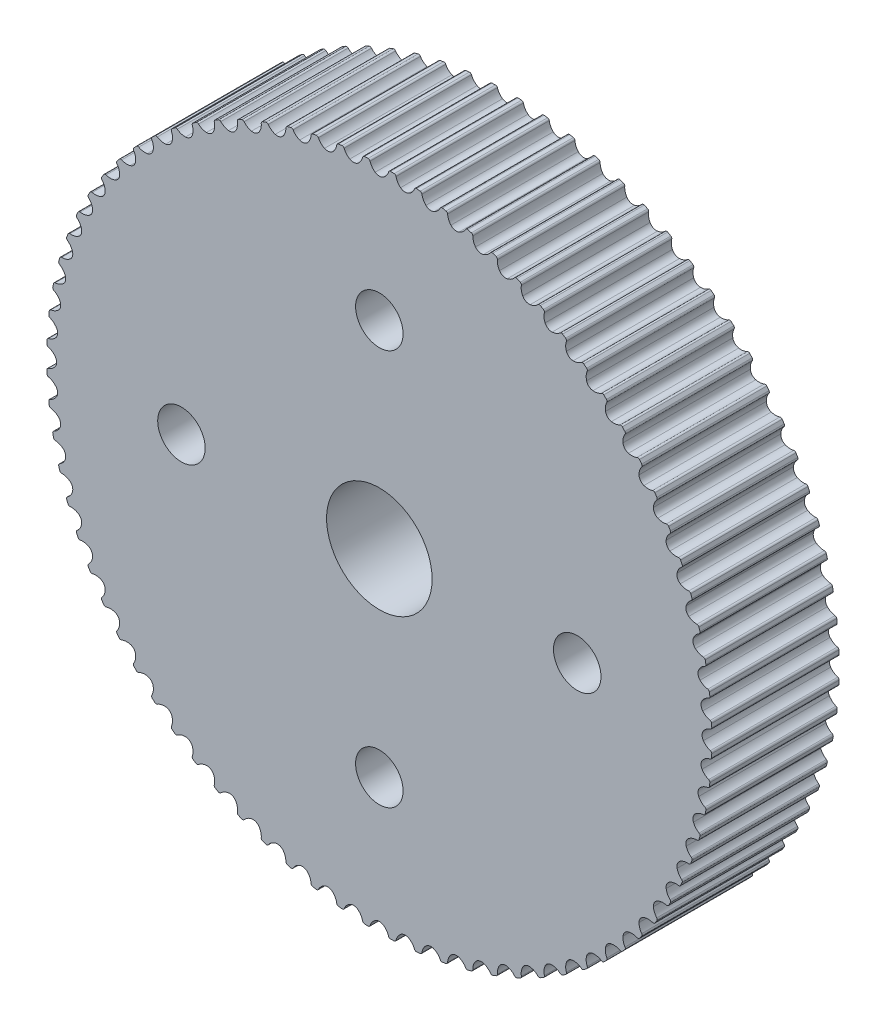
SolidWorks part; units mm, degrees
ref_plane "Front Plane" through (0, 0, 0) normal (0, 0, 1) x (1, 0, 0)
ref_plane "Top Plane" through (0, 0, 0) normal (0, 1, 0) x (1, 0, 0)
ref_plane "Right Plane" through (0, 0, 0) normal (1, 0, 0) x (0, 0, -1)
sketch "Sketch1" plane through (0, 0, 0) normal (0, 0, 1) x (1, 0, 0)
  line L3 (0, 25.2095) -> (1.9984, 25.1302) construction
  line L4 (0, 0) -> (0, 24.4595) construction
  line L5 (0, 24.4595) -> (0, 25.741) construction
  line L15 (1.9984, 25.1302) -> (2.047, 25.741)
  line L16 (2.047, 25.741) -> (-2.047, 25.741)
  line L17 (0, 24.4595) -> (0.1538, 24.4595) construction
  line L18 (-1.9984, 25.1302) -> (-2.047, 25.741)
  circle A0 centre (0, 0) radius 25.4635 construction
  circle A1 centre (0, 0) radius 25.2095 construction
  circle A2 centre (0, 0) radius 24.9555 construction
  arc A10 (0.8513, 25.1951) -> (1.9984, 25.1302) centre (0, 0) cw
  arc A11 (-0.3168, 24.5588) -> (0.3168, 24.5588) centre (0, 25.0145) ccw
  arc A12 (0.3168, 24.5588) -> (0.7027, 25.0889) centre (-0.254, 25.3799) ccw
  arc A13 (0.7027, 25.0889) -> (0.8513, 25.1951) centre (0.8462, 25.0452) cw
  arc A14 (-0.8513, 25.1951) -> (-1.9984, 25.1302) centre (0, 0) ccw
  arc A15 (-0.7027, 25.0889) -> (-0.8513, 25.1951) centre (-0.8462, 25.0452) ccw
  arc A16 (-0.3168, 24.5588) -> (-0.7027, 25.0889) centre (0.254, 25.3799) cw
  point P11 (0, 25.4635)
  point P13 (0, 25.2095)
  point P14 (0, 24.9555)
  dimension "D2" = 0.2775
sketch "Sketch2" plane through (0, 0, 0) normal (1, 0, 0) x (0, 0, -1)
  line L0 (-9.525, 4) -> (9.525, 4)
  line L1 (-9.525, 4) -> (-9.525, 19.05)
  line L2 (-9.525, 19.05) -> (-0.125, 19.05)
  line L3 (-0.125, 19.05) -> (-0.125, 25.2095)
  line L9 (9.525, 25.2095) -> (9.525, 4)
  line L10 (-9.525, 0) -> (9.525, 0) construction
  line L16 (-0.125, 25.2095) -> (9.525, 25.2095)
  point P25 (9.525, 0)
  point P26 (-0.125, 0)
  dimension "OA" = 19.05
  dimension "Bore" = 8
  dimension "Hub Dia" = 38.1
  dimension "Outside Width" = 9.65
revolve "Revolve1" add sketch "Sketch2" angle 360 mid plane about L10
sketch "Sketch3" plane through (0, 0, 0) normal (0, 0, 1) x (1, 0, 0)
  line L3 (1.9984, 25.1302) -> (2.047, 25.741) construction
  line L4 (-1.9984, 25.1302) -> (-2.047, 25.741) construction
  line L5 (2.047, 25.741) -> (-2.047, 25.741) construction
  line L6 (1.9984, 25.1302) -> (2.047, 25.741)
  line L7 (-1.9984, 25.1302) -> (-2.047, 25.741)
  line L8 (2.047, 25.741) -> (-2.047, 25.741)
  arc A0 (1.9984, 25.1302) -> (0.8513, 25.1951) centre (0, 0) ccw construction
  arc A1 (0.8513, 25.1951) -> (0.7027, 25.0889) centre (0.8462, 25.0452) ccw construction
  arc A3 (0.3168, 24.5588) -> (0.7027, 25.0889) centre (-0.254, 25.3799) ccw construction
  arc A4 (-0.3168, 24.5588) -> (0.3168, 24.5588) centre (0, 25.0145) ccw construction
  arc A5 (-0.7027, 25.0889) -> (-0.3168, 24.5588) centre (0.254, 25.3799) ccw construction
  arc A6 (-0.7027, 25.0889) -> (-0.8513, 25.1951) centre (-0.8462, 25.0452) ccw construction
  arc A7 (-0.8513, 25.1951) -> (-1.9984, 25.1302) centre (0, 0) ccw construction
  arc A8 (1.9984, 25.1302) -> (0.8513, 25.1951) centre (0, 0) ccw
  arc A9 (0.8513, 25.1951) -> (0.7027, 25.0889) centre (0.8462, 25.0452) ccw
  arc A10 (0.3168, 24.5588) -> (0.7027, 25.0889) centre (-0.254, 25.3799) ccw
  arc A11 (-0.3168, 24.5588) -> (0.3168, 24.5588) centre (0, 25.0145) ccw
  arc A12 (-0.7027, 25.0889) -> (-0.3168, 24.5588) centre (0.254, 25.3799) ccw
  arc A13 (-0.7027, 25.0889) -> (-0.8513, 25.1951) centre (-0.8462, 25.0452) ccw
  arc A14 (-0.8513, 25.1951) -> (-1.9984, 25.1302) centre (0, 0) ccw
extrude "Cut-Extrude1" cut sketch "Sketch3" against normal through all from surface starting at face at (19.05, 0, 0.125)
pattern_circular "CirPattern1" count 80 over 360 about axis through (0, 0, 9.525) along (0, 0, 1) of "Cut-Extrude1"
sketch "Sketch4" plane through (0, 0, 0) normal (1, 0, 0) x (0, 0, -1)
  line L0 (-9.525, 0) -> (-0.125, 0) construction
  line L1 (-9.525, 19.05) -> (-9.525, -19.05) construction
  line L2 (-0.125, 19.05) -> (-0.125, -19.05) construction
  circle A0 centre (-4.825, 0) radius 2.0828
  dimension "D1" = 4.1656
extrude "Cut-Extrude2" cut sketch "Sketch4" along normal through all
ref_plane "Plane1" through (0, 0, 4.825) normal (0, 0, 1) x (1, 0, 0)
sketch "Sketch5" plane through (0, 0, 4.825) normal (0, 0, 1) x (1, 0, 0)
  line L0 (3.415, -2.0828) -> (18.9358, -2.0828) construction
  line L1 (4.381, -2.0828) -> (18.5548, -2.0828)
  line L2 (18.9358, -1.7018) -> (18.9358, 0)
  line L3 (18.9358, 0) -> (4, 0) construction
  line L4 (4, -1.7018) -> (4, 0)
  line L5 (4.381, -2.0828) -> (4, -1.7018)
  line L6 (18.5548, -2.0828) -> (18.9358, -1.7018)
  line L13 (3.415, -2.0828) -> (18.9358, -2.0828) construction
  line L23 (4, 0) -> (18.9358, 0)
  circle A0 centre (0, 0) radius 19.05 construction
  circle A1 centre (0, 0) radius 4 construction
  point P0 (4, -2.0828)
  point P3 (18.9358, -2.0828)
  point P4 (-19.05, 0)
  point P6 (-4, 0)
ref_axis "Center Axis 1" through (0, 0, -9.525) along (0, 0, 1)
ref_plane "Contact Plane 1" through (0, 0, 9.525) normal (0, 0, 1) x (1, 0, 0)
ref_plane "Contact Plane 2" through (0, 0, -9.525) normal (0, 0, -1) x (-1, 0, 0)
sketch "Sketch6" plane through (0, 0, 0.125) normal (0, 0, 1) x (1, 0, 0)
  line L1 (25.4, -25.4) -> (-25.4, -25.4)
  line L2 (25.4, -25.4) -> (25.4, 25.4)
  line L3 (25.4, 25.4) -> (-25.4, 25.4)
  line L4 (-25.4, -25.4) -> (-25.4, 25.4)
  line L5 (25.4, -25.4) -> (-25.4, 25.4) construction
  line L6 (25.4, 25.4) -> (-25.4, -25.4) construction
  circle A0 centre (0, 0) radius 4 construction
  circle A1 centre (0, 0) radius 4
  point P0 (0, 0)
  dimension "D1" = 50.8
  dimension "D2" = 50.8
sketch "Sketch12" plane through (0, 0, 0.125) normal (0, 0, 1) x (1, 0, 0)
  circle A0 centre (0, 0) radius 19.05
  circle A1 centre (0, 0) radius 19.05 construction
extrude "Cut-Extrude4" cut sketch "Sketch12" along normal up to next
hole_wizard "M3 Clearance Hole1" positions "Sketch13" profile "Sketch14" hole size "M3" standard "ANSI Metric" end condition through all
sketch "Sketch13" plane through (0, 0, -9.525) normal (0, 0, -1) x (-1, 0, 0)
  circle A2 centre (0, 0) radius 15
  point P0 (0, 15)
  point P2 (15, 0)
  point P4 (0, -15)
  point P6 (-15, 0)
  dimension "D1" = 30
sketch "Sketch14" plane through (0, 15, -9.525) normal (1, 0, 0) x (0, 1, 0)
  line L0 (0, 0) -> (0, 9.65)
  line L1 (0, 9.65) -> (1.8, 9.65)
  line L2 (1.8, 9.65) -> (1.8, 0)
  line L5 (1.8, 0) -> (0, 0)
  line L11 (0, -6.35) -> (0, 107.95) construction
  dimension "Thru Hole Dia." = 3.6
  dimension "Thru Hole Depth" = 9.65
equation "\"D2@Sketch1\" = \"R3@Sketch1\"/2"
